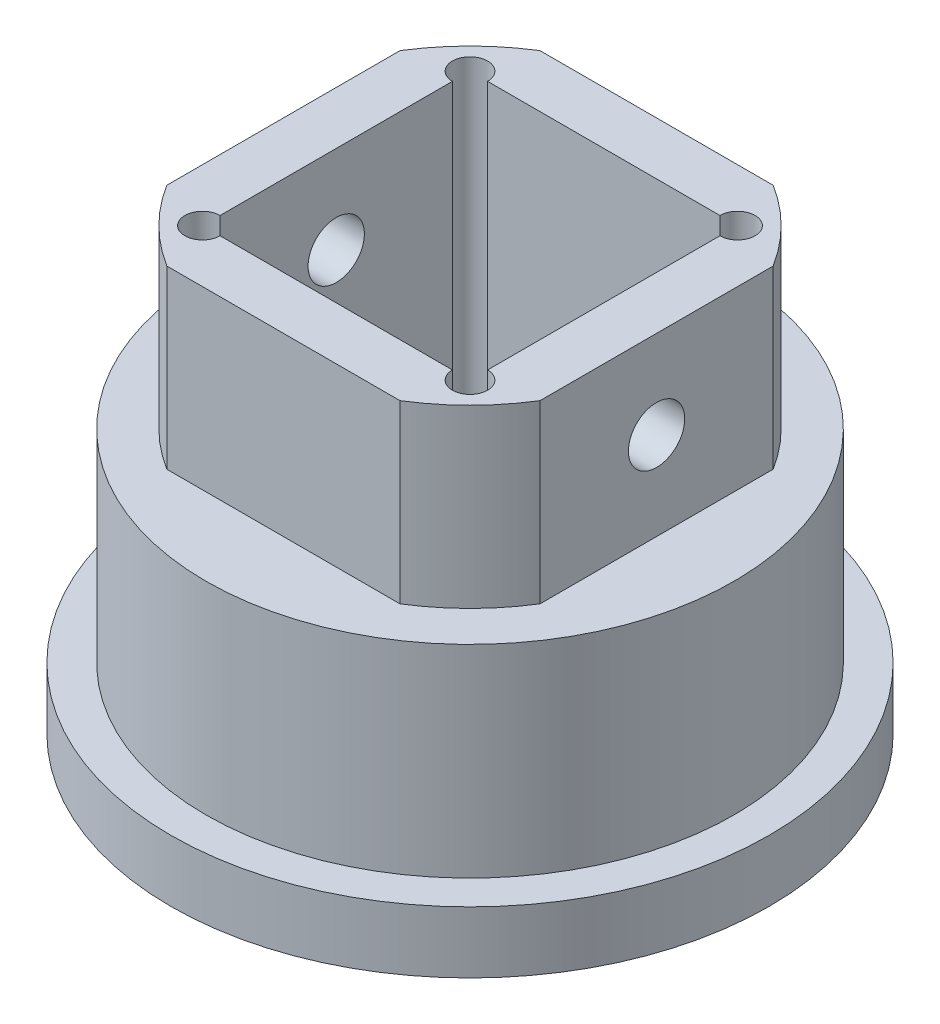
SolidWorks part; units mm, degrees
ref_plane "前视基准面" through (0, 0, 0) normal (0, 0, 1) x (1, 0, 0)
ref_plane "上视基准面" through (0, 0, 0) normal (0, 1, 0) x (1, 0, 0)
ref_plane "右视基准面" through (0, 0, 0) normal (1, 0, 0) x (0, 0, -1)
sketch "草图1" plane through (0, 0, 0) normal (0, 1, 0) x (1, 0, 0)
  line L1 (-7.6, -7.6) -> (7.6, -7.6)
  line L2 (-7.6, -7.6) -> (-7.6, 7.6)
  line L3 (-7.6, 7.6) -> (7.6, 7.6)
  line L4 (7.6, -7.6) -> (7.6, 7.6)
  line L5 (-7.6, -7.6) -> (7.6, 7.6) construction
  line L6 (-7.6, 7.6) -> (7.6, -7.6) construction
  circle A0 centre (0, 0) radius 12.5
  circle A1 centre (7.6, 7.6) radius 1
  circle A2 centre (7.6, -7.6) radius 1
  circle A3 centre (-7.6, -7.6) radius 1
  circle A4 centre (-7.6, 7.6) radius 1
  point P0 (0, 0)
  dimension "D3" = 25
  dimension "D4" = 2
  dimension "D5" = 2
  dimension "D6" = 2
  dimension "D7" = 2
  dimension "D1" = 15.2
  dimension "D2" = 15.2
extrude "凸台-拉伸1" add sketch "草图1" along normal mid plane 15 contours A0 A4 L3 A1 L4 A2 L1 A3 L2 region at (-12.1464, 0, 0)
sketch "草图2" plane through (0, -7.5, 0) normal (0, -1, 0) x (1, 0, 0)
  line L1 (-10.6, -10.6) -> (10.6, -10.6)
  line L2 (-10.6, -10.6) -> (-10.6, 10.6)
  line L3 (-10.6, 10.6) -> (10.6, 10.6)
  line L4 (10.6, -10.6) -> (10.6, 10.6)
  line L5 (-10.6, -10.6) -> (10.6, 10.6) construction
  line L6 (-10.6, 10.6) -> (10.6, -10.6) construction
  line L7 (-7.6, -7.6) -> (7.6, -7.6)
  line L8 (-7.6, -7.6) -> (-7.6, 7.6)
  line L9 (-7.6, 7.6) -> (7.6, 7.6)
  line L10 (7.6, -7.6) -> (7.6, 7.6)
  line L11 (-7.6, -7.6) -> (7.6, 7.6) construction
  line L12 (-7.6, 7.6) -> (7.6, -7.6) construction
  circle A1 centre (7.6, 7.6) radius 1
  circle A2 centre (-7.6, 7.6) radius 1
  circle A3 centre (-7.6, -7.6) radius 1
  circle A4 centre (7.6, -7.6) radius 1
  point P0 (0, 0)
  point P8 (0, 0)
  arc M9 (-6.6, -7.6) -> (-7.6, -6.6) centre (-7.6, -7.6) cw
  line M10 (-7.6, -6.6) -> (-7.6, 6.6)
  arc M11 (-7.6, 6.6) -> (-6.6, 7.6) centre (-7.6, 7.6) cw
  line M12 (-6.6, 7.6) -> (6.6, 7.6)
  arc M13 (6.6, 7.6) -> (7.6, 6.6) centre (7.6, 7.6) cw
  line M14 (7.6, 6.6) -> (7.6, -6.6)
  arc M15 (7.6, -6.6) -> (6.6, -7.6) centre (7.6, -7.6) cw
  line M16 (6.6, -7.6) -> (-6.6, -7.6)
  circle M17 centre (0, 0) radius 12.5
  dimension "D5" = 2
  dimension "D6" = 2
  dimension "D7" = 2
  dimension "D8" = 2
  dimension "D1" = 15.2
  dimension "D2" = 15.2
  dimension "D3" = 3
  dimension "D4" = 3
extrude "凸台-拉伸2" add sketch "草图2" along normal blind 10 contours L4 L3 L2 L1 M17 M16 M9 M10 M11 M12 M13 M14 M15 region at (-8.6268, -7.5, -8.6268)
mirror "镜向1" about plane through (0, 0, 0) normal (0, 1, 0) of "凸台-拉伸2"
sketch "草图3" plane through (0, -7.5, 0) normal (0, -1, 0) x (1, 0, 0)
  circle A0 centre (0, 0) radius 17
  circle A1 centre (0, 0) radius 12.5
  dimension "D1" = 34
  dimension "D2" = 25
extrude "凸台-拉伸3" add sketch "草图3" against normal blind 3
sketch "草图4" plane through (0, 0, 10.6) normal (0, 0, 1) x (1, 0, 0)
  line L0 (-6.625, -12.5) -> (6.625, -12.5) construction
  line L1 (-6.625, -17.5) -> (-6.625, -7.5) construction
  line L2 (6.625, -17.5) -> (6.625, -7.5) construction
  line L3 (0, 0) -> (0, -12.5) construction
  circle A0 centre (0, -12.5) radius 2.1
  dimension "D1" = 4.2
extrude "切除-拉伸1" cut sketch "草图4" against normal through all
sketch "草图5" plane through (10.6, 0, 0) normal (1, 0, 0) x (0, 0, -1)
  line L0 (-6.625, 12.5) -> (6.625, 12.5) construction
  line L1 (-6.625, 17.5) -> (-6.625, 7.5) construction
  line L2 (6.625, 17.5) -> (6.625, 7.5) construction
  circle A0 centre (0, 12.5) radius 1.6
  dimension "D1" = 3.2
extrude "切除-拉伸2" cut sketch "草图5" against normal through all
sketch "草图6" plane through (0, -17.5, 0) normal (0, -1, 0) x (1, 0, 0)
  line L4 (10.6, -6.625) -> (10.6, 6.625)
  line L5 (6.625, 10.6) -> (-6.625, 10.6)
  line L6 (-10.6, 6.625) -> (-10.6, -6.625)
  line L7 (-6.625, -10.6) -> (6.625, -10.6)
  line L8 (10.6, -6.625) -> (10.6, 6.625)
  line L9 (6.625, 10.6) -> (-6.625, 10.6)
  line L10 (-10.6, 6.625) -> (-10.6, -6.625)
  line L11 (-6.625, -10.6) -> (6.625, -10.6)
  arc A4 (6.625, -10.6) -> (10.6, -6.625) centre (0, 0) ccw
  arc A5 (10.6, 6.625) -> (6.625, 10.6) centre (0, 0) ccw
  arc A6 (-6.625, 10.6) -> (-10.6, 6.625) centre (0, 0) ccw
  arc A7 (-10.6, -6.625) -> (-6.625, -10.6) centre (0, 0) ccw
  arc A8 (6.625, -10.6) -> (10.6, -6.625) centre (0, 0) ccw
  arc A9 (10.6, 6.625) -> (6.625, 10.6) centre (0, 0) ccw
  arc A10 (-6.625, 10.6) -> (-10.6, 6.625) centre (0, 0) ccw
  arc A11 (-10.6, -6.625) -> (-6.625, -10.6) centre (0, 0) ccw
  dimension "D1" = 0
extrude "切除-拉伸3" cut sketch "草图6" against normal blind 10
sketch "草图7" plane through (0, -4.5, 0) normal (0, 1, 0) x (1, 0, 0)
  circle A0 centre (0, 0) radius 17 construction
  circle A1 centre (0, 0) radius 17
  circle A3 centre (0, 0) radius 12.5
extrude "凸台-拉伸4" add sketch "草图7" along normal blind 0.5
sketch "草图8" plane through (0, -4, 0) normal (0, 1, 0) x (1, 0, 0)
  circle A0 centre (0, 0) radius 15
  circle A1 centre (0, 0) radius 12.5
  dimension "D1" = 30
extrude "凸台-拉伸5" add sketch "草图8" along normal up to surface (11.5 mm away) up to face at (-11.55, 7.5, 0)
